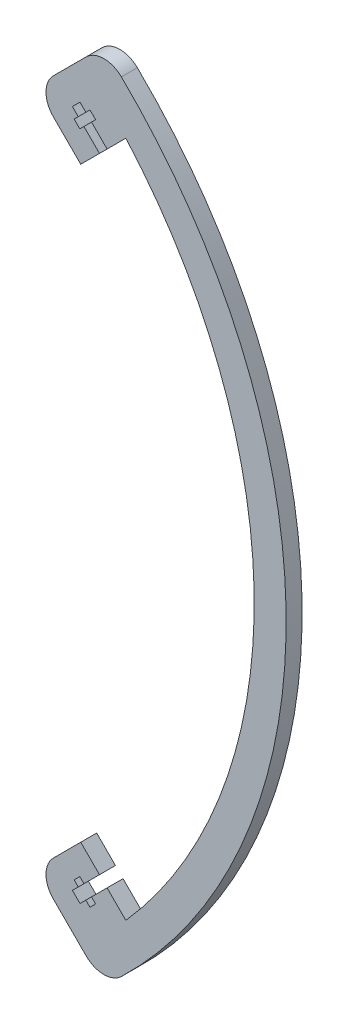
SolidWorks part; units mm, degrees
ref_plane "Front Plane" through (0, 0, 0) normal (0, 0, 1) x (1, 0, 0)
ref_plane "Top Plane" through (0, 0, 0) normal (0, 1, 0) x (1, 0, 0)
ref_plane "Right Plane" through (0, 0, 0) normal (1, 0, 0) x (0, 0, -1)
sketch "Sketch1" plane through (0, 0, 0) normal (0, 0, 1) x (1, 0, 0)
  line L0 (143.3604, 116.9193) -> (134.3442, 107.9031)
  line L1 (143.3604, -160.8213) -> (134.3442, -151.805)
  line L2 (143.3604, -160.8213) -> (128.1057, -145.5666) construction
  line L3 (128.1057, 101.6647) -> (143.3604, 116.9193) construction
  arc A0 (143.3604, 116.9193) -> (143.3604, -160.8213) centre (-21.951, -21.951) cw
  arc A1 (134.3442, 107.9031) -> (134.3442, -151.805) centre (-21.951, -21.951) cw
  arc A2 (143.3604, 116.9193) -> (131.0145, 130.4116) centre (-21.951, -21.951) ccw construction
  dimension "D1" = 12.7
extrude "Arc Extrusion" add sketch "Sketch1" along normal blind 6.35
ref_plane "Clothes Line Center Plane" through (0, -21.951, 0) normal (0, 1, 0) x (1, 0, 0)
sketch "Sketch4" plane through (0, 0, 6.35) normal (0, 0, 1) x (1, 0, 0)
  line L0 (134.3442, -151.805) -> (143.3604, -160.8213)
  line L1 (139.4438, -165.8849) -> (130.4636, -156.9046) construction
  line L2 (105.6551, -132.0962) -> (123.6156, -150.0567) construction
  line L3 (139.194, -165.6351) -> (112.2532, -138.6943)
  line L4 (112.2532, -138.6943) -> (94.2927, -156.6548)
  line L5 (94.2927, -156.6548) -> (121.204, -183.5661)
  arc A0 (143.3604, -160.8213) -> (139.194, -165.6351) centre (-21.951, -21.951) cw
  arc A1 (134.3442, -151.805) -> (130.1981, -156.6392) centre (-21.951, -21.951) cw
  arc A2 (139.194, -165.6351) -> (121.204, -183.5661) centre (-21.951, -21.951) cw
  arc A3 (134.3442, -151.805) -> (134.3442, 107.9031) centre (-21.951, -21.951) ccw construction
  arc A4 (143.3604, -160.8213) -> (143.3604, 116.9193) centre (-21.951, -21.951) ccw construction
  arc A5 (131.0145, -174.3136) -> (143.3604, -160.8213) centre (-21.951, -21.951) ccw construction
  line M8 (134.3442, -151.805) -> (143.3604, -160.8213)
  dimension "D1" = 25.4
  dimension "D2" = 38.1
extrude "Mount to V Funnel" add sketch "Sketch4" against normal up to surface (6.35 mm away) contours A1 L3 A0 M8 | A2 L3 L4 L5 region at (136.7864, -158.7357, 6.35) region at (116.8258, -161.2242, 6.35) up to face at (163.2257, -21.951, 0)
sketch "Sketch5" plane through (0, 0, 6.35) normal (0, 0, 1) x (1, 0, 0)
  line L0 (121.2256, -147.6667) -> (103.2651, -165.6272) construction
  line L1 (130.1981, -156.6392) -> (112.2532, -138.6943) construction
  line L2 (94.2927, -156.6548) -> (121.204, -183.5661) construction
  line L3 (130.1981, -156.6392) -> (112.2376, -174.5997)
  line L4 (112.2532, -138.6943) -> (94.2927, -156.6548) construction
  line B0 (122.7343, -149.1754) -> (119.717, -146.158)
  line B1 (111.2755, -154.5995) -> (109.6411, -152.9651)
  line B2 (109.6411, -152.9651) -> (111.8862, -150.72)
  line B3 (111.8862, -150.72) -> (113.5206, -152.3544)
  line B4 (113.5206, -152.3544) -> (119.717, -146.158)
  line B5 (111.2755, -154.5995) -> (108.9406, -156.9344)
  line B6 (108.9406, -156.9344) -> (111.958, -159.9517)
  line B7 (114.2929, -157.6169) -> (111.958, -159.9517)
  line B8 (116.5379, -155.3718) -> (122.7343, -149.1754)
  line B9 (118.1723, -157.0062) -> (116.5379, -155.3718)
  line B10 (115.9273, -159.2513) -> (118.1723, -157.0062)
  line B11 (114.2929, -157.6169) -> (115.9273, -159.2513)
  line M9 (130.1981, -156.6392) -> (112.2532, -138.6943)
sketch_block_instance "TSlot-1"
sketch_block "TSlot" parameters "D1"=3.302, "D2"=3.175
extrude "T Slot Hole" cut sketch "Sketch5" against normal through all contours L0 B6 B7 B11 B10 B9 B8 M9 | L0 B0 B4 B3 B2 B1 B5 B6 region at (116.5257, -154.4541, 6.35) region at (114.4382, -152.3667, 6.35)
mirror "Mount and T Slot Mirror" about plane through (0, -21.951, 0) normal (0, 1, 0) of "Mount to V Funnel", "T Slot Hole"
fillet "Mount Fillets" radius 10 4 edges at (94.2927, -156.6548, 3.175) (121.204, -183.5661, 3.175) (94.2927, 112.7529, 3.175) (121.204, 139.6642, 3.175)
